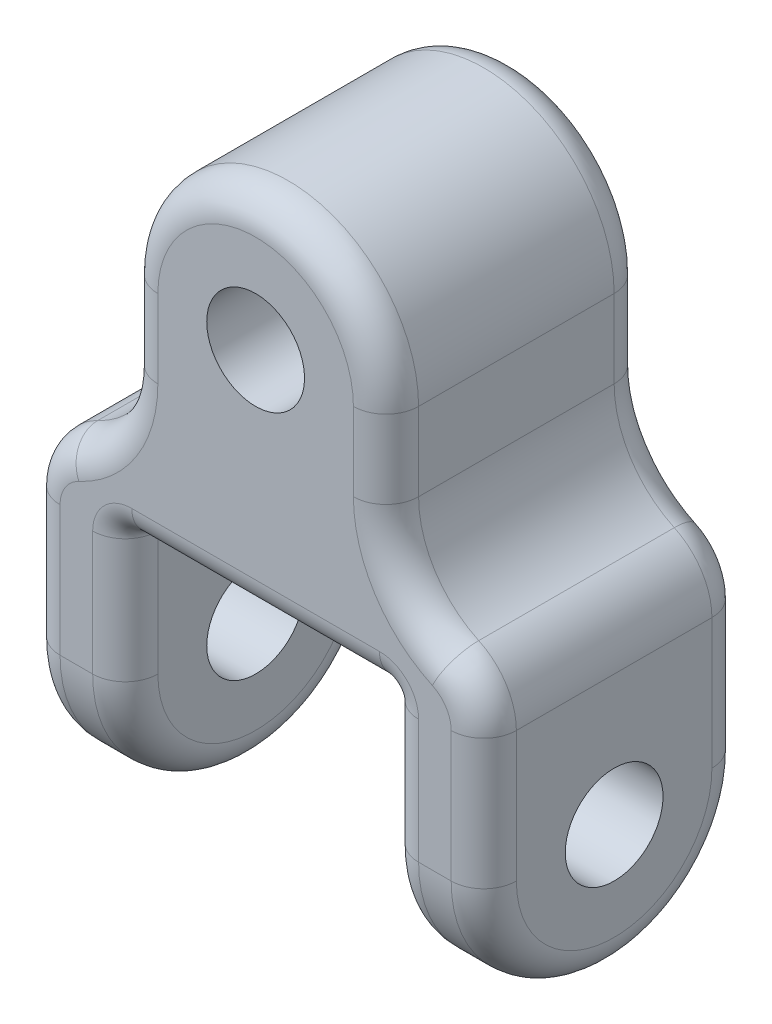
SolidWorks part; units mm, degrees
ref_plane "Front Plane" through (0, 0, 0) normal (0, 0, 1) x (1, 0, 0)
ref_plane "Top Plane" through (0, 0, 0) normal (0, 1, 0) x (1, 0, 0)
ref_plane "Right Plane" through (0, 0, 0) normal (1, 0, 0) x (0, 0, -1)
sketch "Sketch1" plane through (0, 0, 0) normal (0, 0, 1) x (1, 0, 0)
  line L0 (0, 0) -> (0, 94.1096) construction
  line L1 (-30, 60) -> (-30, 0)
  line L2 (-30, 0) -> (-52.5, 0)
  line L3 (-52.5, 0) -> (-52.5, 60)
  line L4 (-30, 95.3377) -> (-30, 113.3377)
  line L5 (30, 0) -> (52.5, 0)
  line L6 (30, 60) -> (30, 0)
  line L7 (52.5, 0) -> (52.5, 60)
  line L8 (30, 95.3377) -> (30, 113.3377)
  line L9 (30, 60) -> (-30, 60)
  arc A0 (-52.5, 60) -> (-43.8462, 73.5914) centre (-37.5, 60) cw
  arc A1 (-43.8462, 73.5914) -> (-30, 95.3377) centre (-54, 95.3377) ccw
  arc A2 (-30, 113.3377) -> (30, 113.3377) centre (0, 113.3377) cw
  arc A3 (52.5, 60) -> (43.8462, 73.5914) centre (37.5, 60) ccw
  arc A4 (43.8462, 73.5914) -> (30, 95.3377) centre (54, 95.3377) cw
  point P14 (-50.1529, 68.0563)
  point P20 (50.1529, 68.0563)
  dimension "D1" = 60
  dimension "D6" = 24
  dimension "D8" = 30
  dimension "D2" = 30
  dimension "D3" = 22.5
  dimension "D4" = 60
  dimension "D5" = 15
  dimension "D7" = 18
extrude "Boss-Extrude1" add sketch "Sketch1" along normal blind 60
fillet "Fillet2" 2 edges at (41.25, 0, 60) (41.25, 0, 0) type full round first side face at (0, 59.5015, 60) second side face at (0, 59.5015, 0) middle face at (41.25, 0, 30)
fillet "Fillet3" 2 edges at (-41.25, 0, 0) (-41.25, 0, 60) type full round first side face at (0, 63.7872, 0) second side face at (0, 63.7872, 60) middle face at (-41.25, 0, 30)
sketch "Sketch2" plane through (52.5, 0, 0) normal (1, 0, 0) x (0, 0, -1)
  circle A0 centre (-30, 30) radius 11.25
  arc A1 (-60, 30) -> (0, 30) centre (-30, 30) ccw construction
  point P7 (-30, 0)
  dimension "D1" = 22.5
  dimension "D2" = 30
  dimension "D3" = 30
extrude "Cut-Extrude1" cut sketch "Sketch2" against normal through all both and the other way through all
sketch "Sketch3" plane through (0, 0, 0) normal (0, 0, -1) x (-1, 0, 0)
  circle A0 centre (0, 113.3377) radius 11.25
  arc A1 (30, 113.3377) -> (-30, 113.3377) centre (0, 113.3377) ccw construction
  point P7 (0, 143.3377)
  dimension "D1" = 22.5
  dimension "D2" = 30
  dimension "D3" = 30
extrude "Cut-Extrude2" cut sketch "Sketch3" against normal through all
fillet "Fillet4" radius 1.5 2 edges at (-30, 60, 30) (30, 60, 30)
fillet "Fillet6" radius 7.5 32 edges at (-50.1529, 68.0563, 0) (-33.7553, 82.4476, 0) (-30, 104.3377, 0) (0, 143.3377, 0) (30, 104.3377, 0) (33.7553, 82.4476, 0) (50.1529, 68.0563, 0) (52.5, 0, 30) (52.5, 45, 60) (50.1529, 68.0563, 60) (33.7553, 82.4476, 60) (30, 104.3377, 60) (0, 143.3377, 60) (-30, 104.3377, 60) (-33.7553, 82.4476, 60) (-50.1529, 68.0563, 60) (-52.5, 45, 60) (-52.5, 0, 30) (-30, 0, 30) (-30, 44.25, 60) (-29.5607, 59.5607, 60) (0, 60, 60) (29.5607, 59.5607, 60) (30, 44.25, 60) (30, 0, 30) (30, 44.25, 0) (29.5607, 59.5607, 0) (0, 60, 0) (-29.5607, 59.5607, 0) (52.5, 45, 0) (-52.5, 45, 0) (-30, 44.25, 0)
